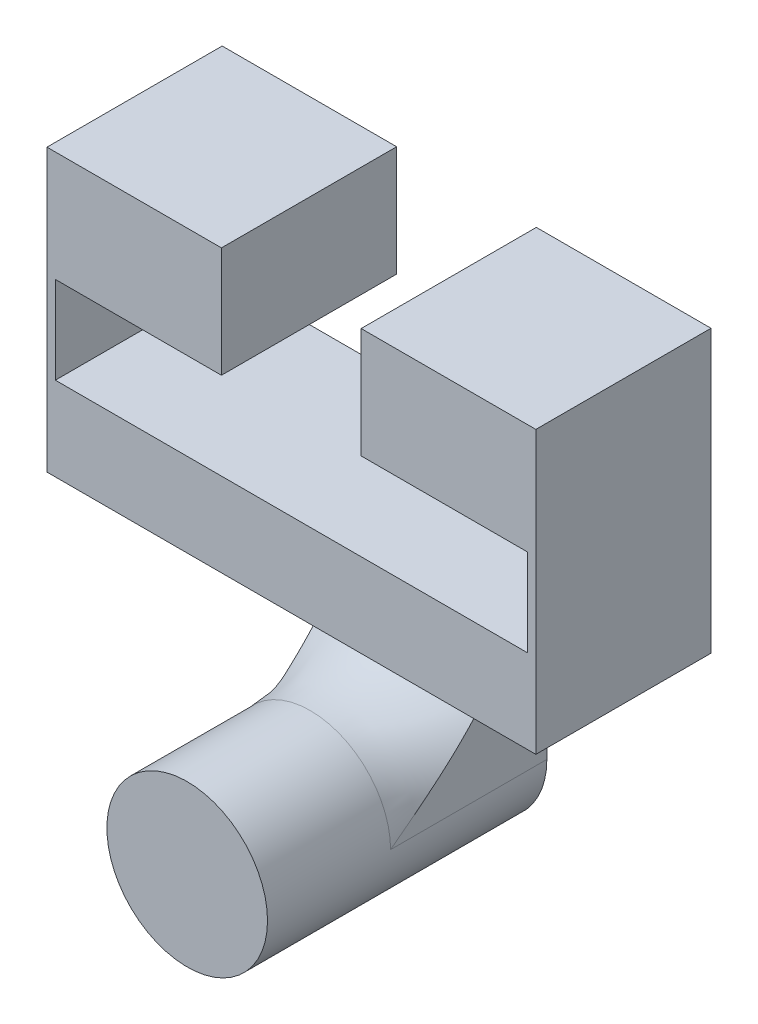
SolidWorks part; units mm, degrees
material "6061-T6 (SS)"
ref_plane "Front Plane" through (0, 0, 0) normal (0, 0, 1) x (1, 0, 0)
ref_plane "Top Plane" through (0, 0, 0) normal (0, 1, 0) x (1, 0, 0)
ref_plane "Right Plane" through (0, 0, 0) normal (1, 0, 0) x (0, 0, -1)
sketch "Sketch1" plane through (0, 0, 0) normal (0, 0, 1) x (1, 0, 0)
  circle A0 centre (0, 0) radius 14.605
extrude "Boss-Extrude1" add sketch "Sketch1" against normal blind 50.8 contours A0
sketch "Sketch2" plane through (0, 0, -50.8) normal (0, 0, -1) x (-1, 0, 0)
  line L1 (-14.605, 0) -> (14.605, 0)
  line L2 (-14.605, 0) -> (-14.605, 31.6499)
  line L3 (-14.605, 31.6499) -> (14.605, 31.6499)
  line L4 (14.605, 0) -> (14.605, 31.6499)
  circle A0 centre (0, 0) radius 14.605 construction
extrude "Boss-Extrude3" add sketch "Sketch2" against normal blind 3.0201
sketch "Sketch3" plane through (0, 31.6499, 0) normal (0, 1, 0) x (1, 0, 0)
  line L0 (-14.605, 50.8) -> (-44.4425, 50.8)
  line L1 (-44.4425, 50.8) -> (-44.4425, 18.942)
  line L2 (-44.4425, 18.942) -> (44.4575, 18.942)
  line L3 (44.4575, 18.942) -> (44.4575, 50.8)
  line L4 (44.4575, 50.8) -> (-14.605, 50.8)
extrude "Boss-Extrude4" add sketch "Sketch3" along normal blind 15.24
sketch "Sketch4" plane through (0, 46.8899, 0) normal (0, 1, 0) x (1, 0, 0)
  line L0 (44.4575, 50.8) -> (42.9335, 50.8)
  line L1 (44.4575, 50.8) -> (-44.4425, 50.8) construction
  line L2 (42.9335, 50.8) -> (42.9335, 18.942)
  line L3 (-44.4425, 18.942) -> (44.4575, 18.942) construction
  line L4 (42.9335, 18.942) -> (44.4575, 18.942)
  line L5 (44.4575, 18.942) -> (44.4575, 50.8)
  line L6 (-44.4425, 50.8) -> (-44.4425, 18.942)
  line L7 (-44.4425, 18.942) -> (-42.9185, 18.942)
  line L8 (-42.9185, 18.942) -> (-42.9185, 50.8)
  line L9 (-42.9185, 50.8) -> (-44.4425, 50.8)
extrude "Boss-Extrude6" add sketch "Sketch4" along normal blind 15.875
sketch "Sketch5" plane through (0, 62.7649, 0) normal (0, 1, 0) x (1, 0, 0)
  line L0 (-44.4425, 50.8) -> (-12.7159, 50.8)
  line L1 (42.9335, 50.8) -> (-42.9185, 50.8) construction
  line L2 (-12.7159, 50.8) -> (-12.7159, 18.942)
  line L3 (-42.9185, 18.942) -> (42.9335, 18.942) construction
  line L4 (-12.7159, 18.942) -> (-44.4425, 18.942)
  line L5 (-44.4425, 18.942) -> (-44.4425, 50.8)
  line L6 (44.4575, 50.8) -> (12.6898, 50.8)
  line L7 (12.6898, 50.8) -> (12.6898, 18.942)
  line L8 (12.6898, 18.942) -> (44.4575, 18.942)
  line L9 (44.4575, 18.942) -> (44.4575, 50.8)
extrude "Boss-Extrude7" add sketch "Sketch5" along normal blind 20.066
fillet "Fillet2" radius 25.4 1 edges at (0, 14.605, -47.7799)
fillet "Fillet5" radius 5.08 1 edges at (0, 31.6499, -46.3664)
